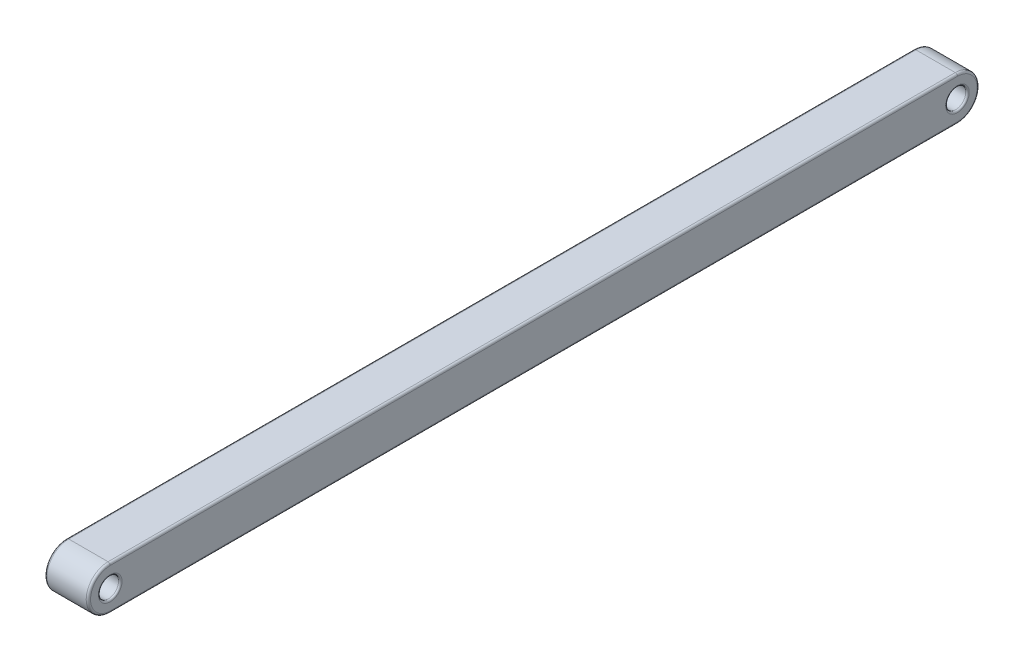
SolidWorks part; units mm, degrees
ref_plane "Front Plane" through (0, 0, 0) normal (0, 0, 1) x (1, 0, 0)
ref_plane "Top Plane" through (0, 0, 0) normal (0, 1, 0) x (1, 0, 0)
ref_plane "Right Plane" through (0, 0, 0) normal (1, 0, 0) x (0, 0, -1)
sketch "Sketch1" plane through (0, 0, 0) normal (1, 0, 0) x (0, 0, -1)
  line L1 (0, 0) -> (48.5, 0)
  line L3 (0, -2.5) -> (48.5, -2.5)
  line L8 (0, 0) -> (0, -2.5) construction
  line L12 (48.5, 0) -> (48.5, -2.5) construction
  circle A0 centre (0, -1.25) radius 0.575
  arc A1 (0, -2.5) -> (0, 0) centre (0, -1.25) cw
  circle A2 centre (48.5, -1.25) radius 0.575
  arc A3 (48.5, 0) -> (48.5, -2.5) centre (48.5, -1.25) cw
  dimension "D1" = 1.15
  dimension "D4" = 1.15
  dimension "D5" = 48.5
  dimension "D6" = 2.5
extrude "Boss-Extrude1" add sketch "Sketch1" along normal blind 2.5
fillet "Fillet1" radius 0.125 8 edges at (2.5, -2.5, -24.25) (0, -2.5, -24.25) (0, 0, -24.25) (2.5, 0, -24.25) (0, -1.25, -49.75) (2.5, -1.25, -49.75) (0, -1.25, 1.25) (2.5, -1.25, 1.25)
fillet "Fillet2" radius 0.1 4 edges at (0, -1.25, -0.575) (2.5, -1.25, -0.575) (0, -1.25, -49.075) (2.5, -1.25, -49.075)
